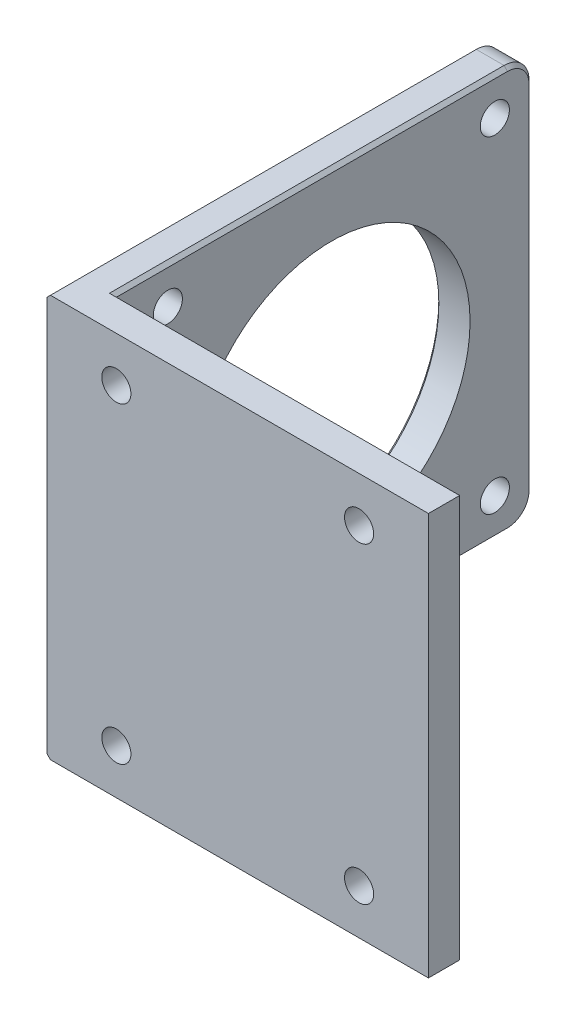
SolidWorks part; units mm, degrees
material "6061 Alloy"
ref_plane "Front Plane" through (0, 0, 0) normal (0, 0, 1) x (1, 0, 0)
ref_plane "Top Plane" through (0, 0, 0) normal (0, 1, 0) x (1, 0, 0)
ref_plane "Right Plane" through (0, 0, 0) normal (1, 0, 0) x (0, 0, -1)
sketch "Sketch2" plane through (0, 0, 0) normal (0, 1, 0) x (1, 0, 0)
  line L0 (0, 0) -> (0, 65)
  line L1 (0, 65) -> (5, 65)
  line L2 (5, 65) -> (5, 5)
  line L3 (5, 5) -> (55, 5)
  line L4 (55, 5) -> (55, 0)
  line L5 (55, 0) -> (0, 0)
  dimension "D1" = 5
  dimension "D2" = 65
  dimension "D3" = 55
extrude "Boss-Extrude2" add sketch "Sketch2" along normal blind 58
sketch "Sketch3" plane through (5, 0, 0) normal (-1, 0, 0) x (0, 0, 1)
  line L0 (-65, 29) -> (-5, 29) construction
  line L1 (-65, 58) -> (-65, 0) construction
  line L24 (-5, 0) -> (-5, 58) construction
  line L25 (-65, 0) -> (0, 0) construction
  line L26 (-65, 58) -> (0, 58) construction
  line L27 (-5, 58) -> (-5, 0) construction
  circle A0 centre (-36, 29) radius 20
  point P49 (-36, 29)
  dimension "D3" = 40
  dimension "D1" = 29
extrude "Cut-Extrude3" cut sketch "Sketch3" along normal through all
sketch "Sketch5" plane through (0, 0, 0) normal (0, 0, -1) x (-1, 0, 0)
  line L0 (-5, 58) -> (-5, 0) construction
  line L2 (-5, 58) -> (-5, 0) construction
  line L4 (-5, 29) -> (-10, 29) construction
  line L7 (-45, 6.5) -> (-10, 6.5) construction
  line L8 (-45, 6.5) -> (-45, 51.5) construction
  line L9 (-45, 51.5) -> (-10, 51.5) construction
  line L10 (-10, 6.5) -> (-10, 51.5) construction
  line L11 (-45, 6.5) -> (-10, 51.5) construction
  line L12 (-45, 51.5) -> (-10, 6.5) construction
  point P12 (-27.5, 29)
  point P18 (-10, 6.5)
  point P19 (-10, 51.5)
  point P20 (-45, 51.5)
  point P21 (-45, 6.5)
  dimension "D1" = 35
  dimension "D2" = 45
  dimension "D3" = 5
hole_wizard "M5x0.8 Tapped Hole3" positions "Sketch20" profile "Sketch19" tap size "M5x0.8" standard "ANSI Metric" end condition through all
sketch "Sketch20" plane through (0, 0, 0) normal (0, 0, 1) x (1, 0, 0)
  point P0 (10, 6.5)
  point P3 (10, 51.5)
  point P6 (45, 51.5)
  point P9 (45, 6.5)
sketch "Sketch19" plane through (10, 6.5, 0) normal (1, 0, 0) x (0, -1, 0)
  line L0 (0, 0) -> (0, 65)
  line L1 (0, 65) -> (2.1, 65)
  line L2 (2.1, 65) -> (2.1, 0)
  line L5 (2.1, 0) -> (0, 0)
  line L11 (0, -6.35) -> (0, 107.95) construction
  dimension "Thru Tap Drill Dia." = 4.2
  dimension "Thru Tap Drill Depth" = 65
cosmetic thread "Hole Thread9" parameters "D2"=5
cosmetic thread "Hole Thread10" parameters "D2"=5
cosmetic thread "Hole Thread11" parameters "D2"=5
cosmetic thread "Hole Thread12" parameters "D2"=5
sketch "Sketch6" plane through (0, 0, 0) normal (1, 0, 0) x (0, 0, -1)
  line L1 (12.4268, 5.4268) -> (59.5732, 5.4268) construction
  line L2 (12.4268, 5.4268) -> (12.4268, 52.5732) construction
  line L3 (12.4268, 52.5732) -> (59.5732, 52.5732) construction
  line L4 (59.5732, 5.4268) -> (59.5732, 52.5732) construction
  line L5 (12.4268, 5.4268) -> (59.5732, 52.5732) construction
  line L6 (12.4268, 52.5732) -> (59.5732, 5.4268) construction
  circle A0 centre (36, 29) radius 33.3375 construction
  point P0 (36, 29)
  point P7 (12.4268, 52.5732)
  point P8 (59.5732, 52.5732)
  point P9 (59.5732, 5.4268)
  point P10 (12.4268, 5.4268)
  dimension "D1" = 66.675
hole_wizard "M5x0.8 Tapped Hole2" positions "Sketch14" profile "Sketch13" tap size "M5x0.8" standard "ANSI Metric" end condition through all
sketch "Sketch14" plane through (0, 0, 0) normal (-1, 0, 0) x (0, 0, 1)
  point P0 (-12.4268, 5.4268)
  point P3 (-12.4268, 52.5732)
  point P6 (-59.5732, 52.5732)
  point P9 (-59.5732, 5.4268)
sketch "Sketch13" plane through (0, 5.4268, -12.4268) normal (0, 1, 0) x (0, 0, 1)
  line L0 (0, 0) -> (0, 55)
  line L1 (0, 55) -> (2.1, 55)
  line L2 (2.1, 55) -> (2.1, 0)
  line L5 (2.1, 0) -> (0, 0)
  line L11 (0, -6.35) -> (0, 107.95) construction
  dimension "Thru Tap Drill Dia." = 4.2
  dimension "Thru Tap Drill Depth" = 55
cosmetic thread "Hole Thread5" parameters "D2"=5
cosmetic thread "Hole Thread6" parameters "D2"=5
cosmetic thread "Hole Thread7" parameters "D2"=5
cosmetic thread "Hole Thread8" parameters "D2"=5
fillet "Fillet1" radius 3.6 2 edges at (2.5, 58, -65) (2.5, 0, -65)
chamfer "Chamfer1" distance 0.5 angle 45 14 edges at (0, 58, -30.7) (0, 56.9456, -63.9456) (0, 29, -65) (0, 1.0544, -63.9456) (0, 0, -30.7) (5, 58, -33.2) (5, 56.9456, -63.9456) (5, 1.0544, -63.9456) (30, 58, -5) (55, 29, -5) (30, 0, -5) (5, 0, -33.2) (0, 29, -16) (5, 29, -65)
